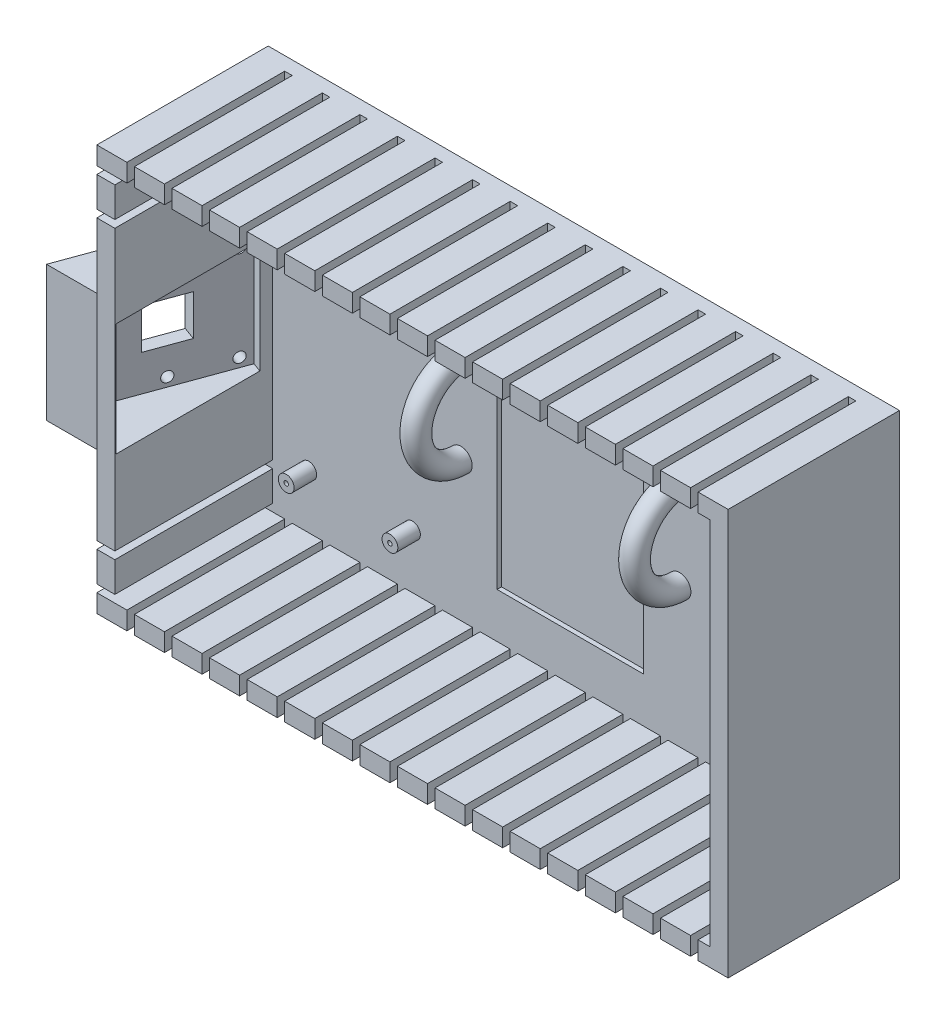
SolidWorks part; units mm, degrees
ref_plane "Front Plane" through (0, 0, 0) normal (1, 0, 0) x (0, 1, 0)
ref_plane "Top Plane" through (0, 0, 0) normal (0, 0, 1) x (0, 1, 0)
ref_plane "Right Plane" through (0, 0, 0) normal (0, 1, 0) x (-1, 0, 0)
sketch "Sketch1" plane through (0, 0, 0) normal (0, 0, 1) x (0, 1, 0)
  line L0 (-45, 0) -> (45, 0) construction
  line L1 (45, -70) -> (-45, -70)
  line L2 (45, -70) -> (45, 70)
  line L3 (45, 70) -> (-45, 70)
  line L4 (-45, -70) -> (-45, 70)
  line L5 (0, 70) -> (0, -70) construction
  point P9 (0, 0)
  dimension "D1" = 140
  dimension "D2" = 90
extrude "Boss-Extrude1" add sketch "Sketch1" along normal blind 3
sketch "Sketch2" plane through (0, 0, 3) normal (0, 0, 1) x (1, 0, 0)
  line L0 (-70, 45) -> (-70, -45) construction
  line L1 (-16.25, 31) -> (16.25, 31)
  line L2 (-16.25, 31) -> (-16.25, -31)
  line L3 (-16.25, -31) -> (16.25, -31)
  line L4 (16.25, 31) -> (16.25, -31)
  line L6 (-70, 0) -> (-16.25, 0) construction
  line L7 (16.25, 0) -> (70, 0) construction
  line L8 (70, -45) -> (70, 45) construction
  line L9 (0, 31) -> (0, 45) construction
  line L10 (70, 45) -> (-70, 45) construction
  line L11 (0, -31) -> (0, -45) construction
  line L12 (-70, -45) -> (70, -45) construction
  dimension "D1" = 62
  dimension "D2" = 32.5
extrude "Cut-Extrude1" cut sketch "Sketch2" against normal blind 1
sketch "Sketch6" plane through (0, 0, 3) normal (0, 0, 1) x (1, 0, 0)
  line L0 (-58, -45) -> (-58, -29) construction
  line L1 (-70, -45) -> (70, -45) construction
  line L2 (-58, 29) -> (-58, 45) construction
  line L3 (70, 45) -> (-70, 45) construction
  line L4 (-70, 45) -> (-70, -45) construction
  circle A0 centre (-58, 29) radius 1.75
  circle A1 centre (-35, 29) radius 1.75
  circle A2 centre (-35, -29) radius 1.75
  circle A3 centre (-58, -29) radius 1.75
  circle A4 centre (-58, 29) radius 0.5
  circle A5 centre (-35, 29) radius 0.5
  circle A6 centre (-58, -29) radius 0.5
  circle A7 centre (-35, -29) radius 0.5
  dimension "D1" = 3.5
  dimension "D2" = 23
  dimension "D3" = 58
  dimension "D4" = 12
  dimension "D5" = 1
extrude "Boss-Extrude2" add sketch "Sketch6" along normal blind 5 contours A1 | A0 | A3 | A2 region at (-59.7005, 29, 3) region at (-36.7005, 29, 3) region at (-36.7005, -29, 3) region at (-59.7005, -29, 3)
extrude "Boss-Extrude3" add sketch "Sketch6<3>" along normal blind 4 contours A4 | A5 | A6 | A7 region at (-58, 29, 3) region at (-35, 29, 3) region at (-58, -29, 3) region at (-35, -29, 3)
sketch "Sketch6<3>" plane through (0, 0, 3) normal (0, 0, 1) x (1, 0, 0) same geometry as "Sketch6"
sketch "Sketch7" plane through (0, 0, 3) normal (0, 0, 1) x (1, 0, 0)
  line L0 (-61.6667, 45) -> (-61.6667, 41)
  line L1 (-70, 45) -> (-63.3333, 45)
  line L2 (-70, 45) -> (-70, 41)
  line L3 (-70, 41) -> (-63.3333, 41)
  line L4 (-63.3333, 45) -> (-63.3333, 41)
  line L5 (-61.6667, 45) -> (-55, 45)
  line L6 (-55, 45) -> (-55, 41)
  line L7 (-61.6667, 41) -> (-55, 41)
  line L8 (-53.3333, 45) -> (-53.3333, 41)
  line L9 (-53.3333, 45) -> (-46.6667, 45)
  line L10 (-46.6667, 45) -> (-46.6667, 41)
  line L11 (-53.3333, 41) -> (-46.6667, 41)
  line L12 (-45, 45) -> (-45, 41)
  line L13 (-45, 45) -> (-38.3333, 45)
  line L14 (-38.3333, 45) -> (-38.3333, 41)
  line L15 (-45, 41) -> (-38.3333, 41)
  line L16 (-36.6667, 45) -> (-36.6667, 41)
  line L17 (-36.6667, 45) -> (-30, 45)
  line L18 (-30, 45) -> (-30, 41)
  line L19 (-36.6667, 41) -> (-30, 41)
  line L20 (-28.3333, 45) -> (-28.3333, 41)
  line L21 (-28.3333, 45) -> (-21.6667, 45)
  line L22 (-21.6667, 45) -> (-21.6667, 41)
  line L23 (-28.3333, 41) -> (-21.6667, 41)
  line L24 (-20, 45) -> (-20, 41)
  line L25 (-20, 45) -> (-13.3333, 45)
  line L26 (-13.3333, 45) -> (-13.3333, 41)
  line L27 (-20, 41) -> (-13.3333, 41)
  line L28 (-11.6667, 45) -> (-11.6667, 41)
  line L29 (-11.6667, 45) -> (-5, 45)
  line L30 (-5, 45) -> (-5, 41)
  line L31 (-11.6667, 41) -> (-5, 41)
  line L32 (-3.3333, 45) -> (-3.3333, 41)
  line L33 (-3.3333, 45) -> (3.3333, 45)
  line L34 (3.3333, 45) -> (3.3333, 41)
  line L35 (-3.3333, 41) -> (3.3333, 41)
  line L36 (5, 45) -> (5, 41)
  line L37 (5, 45) -> (11.6667, 45)
  line L38 (11.6667, 45) -> (11.6667, 41)
  line L39 (5, 41) -> (11.6667, 41)
  line L40 (13.3333, 45) -> (13.3333, 41)
  line L41 (13.3333, 45) -> (20, 45)
  line L42 (20, 45) -> (20, 41)
  line L43 (13.3333, 41) -> (20, 41)
  line L44 (21.6667, 45) -> (21.6667, 41)
  line L45 (21.6667, 45) -> (28.3333, 45)
  line L46 (28.3333, 45) -> (28.3333, 41)
  line L47 (21.6667, 41) -> (28.3333, 41)
  line L48 (30, 45) -> (30, 41)
  line L49 (30, 45) -> (36.6667, 45)
  line L50 (36.6667, 45) -> (36.6667, 41)
  line L51 (30, 41) -> (36.6667, 41)
  line L52 (38.3333, 45) -> (38.3333, 41)
  line L53 (38.3333, 45) -> (45, 45)
  line L54 (45, 45) -> (45, 41)
  line L55 (38.3333, 41) -> (45, 41)
  line L56 (46.6667, 45) -> (46.6667, 41)
  line L57 (46.6667, 45) -> (53.3333, 45)
  line L58 (53.3333, 45) -> (53.3333, 41)
  line L59 (46.6667, 41) -> (53.3333, 41)
  line L60 (55, 45) -> (55, 41)
  line L61 (55, 45) -> (61.6667, 45)
  line L62 (61.6667, 45) -> (61.6667, 41)
  line L63 (55, 41) -> (61.6667, 41)
  line L64 (63.3333, 45) -> (63.3333, 41)
  line L65 (63.3333, 45) -> (70, 45)
  line L66 (70, 45) -> (70, 41)
  line L67 (63.3333, 41) -> (70, 41)
  line L112 (0, 0) -> (0, 18.2112) construction
  line L113 (0, 0) -> (-20.7335, 0) construction
  line L114 (13.3333, -45) -> (20, -45)
  line L115 (20, -45) -> (20, -41)
  line L116 (13.3333, -41) -> (20, -41)
  line L117 (13.3333, -45) -> (13.3333, -41)
  line L118 (21.6667, -45) -> (28.3333, -45)
  line L119 (28.3333, -45) -> (28.3333, -41)
  line L120 (21.6667, -41) -> (28.3333, -41)
  line L121 (21.6667, -45) -> (21.6667, -41)
  line L122 (30, -45) -> (36.6667, -45)
  line L123 (36.6667, -45) -> (36.6667, -41)
  line L124 (30, -41) -> (36.6667, -41)
  line L125 (30, -45) -> (30, -41)
  line L126 (38.3333, -45) -> (45, -45)
  line L127 (45, -45) -> (45, -41)
  line L128 (38.3333, -41) -> (45, -41)
  line L129 (38.3333, -45) -> (38.3333, -41)
  line L130 (46.6667, -45) -> (53.3333, -45)
  line L131 (53.3333, -45) -> (53.3333, -41)
  line L132 (46.6667, -41) -> (53.3333, -41)
  line L133 (46.6667, -45) -> (46.6667, -41)
  line L134 (55, -45) -> (61.6667, -45)
  line L135 (61.6667, -45) -> (61.6667, -41)
  line L136 (55, -41) -> (61.6667, -41)
  line L137 (55, -45) -> (55, -41)
  line L138 (63.3333, -45) -> (70, -45)
  line L139 (70, -45) -> (70, -41)
  line L140 (63.3333, -41) -> (70, -41)
  line L141 (63.3333, -45) -> (63.3333, -41)
  line L142 (5, -45) -> (11.6667, -45)
  line L143 (11.6667, -45) -> (11.6667, -41)
  line L144 (5, -41) -> (11.6667, -41)
  line L145 (5, -45) -> (5, -41)
  line L146 (-3.3333, -45) -> (3.3333, -45)
  line L147 (3.3333, -45) -> (3.3333, -41)
  line L148 (-3.3333, -41) -> (3.3333, -41)
  line L149 (-3.3333, -45) -> (-3.3333, -41)
  line L150 (-11.6667, -45) -> (-5, -45)
  line L151 (-5, -45) -> (-5, -41)
  line L152 (-11.6667, -41) -> (-5, -41)
  line L153 (-11.6667, -45) -> (-11.6667, -41)
  line L154 (-20, -45) -> (-13.3333, -45)
  line L155 (-13.3333, -45) -> (-13.3333, -41)
  line L156 (-20, -41) -> (-13.3333, -41)
  line L157 (-20, -45) -> (-20, -41)
  line L158 (-28.3333, -45) -> (-21.6667, -45)
  line L159 (-21.6667, -45) -> (-21.6667, -41)
  line L160 (-28.3333, -41) -> (-21.6667, -41)
  line L161 (-28.3333, -45) -> (-28.3333, -41)
  line L162 (-36.6667, -45) -> (-30, -45)
  line L163 (-30, -45) -> (-30, -41)
  line L164 (-36.6667, -41) -> (-30, -41)
  line L165 (-36.6667, -45) -> (-36.6667, -41)
  line L166 (-70, -41) -> (-63.3333, -41)
  line L167 (-63.3333, -45) -> (-63.3333, -41)
  line L168 (-70, -45) -> (-63.3333, -45)
  line L169 (-70, -45) -> (-70, -41)
  line L170 (-61.6667, -45) -> (-55, -45)
  line L171 (-55, -45) -> (-55, -41)
  line L172 (-61.6667, -41) -> (-55, -41)
  line L173 (-61.6667, -45) -> (-61.6667, -41)
  line L174 (-53.3333, -45) -> (-46.6667, -45)
  line L175 (-46.6667, -45) -> (-46.6667, -41)
  line L176 (-53.3333, -41) -> (-46.6667, -41)
  line L177 (-53.3333, -45) -> (-53.3333, -41)
  line L178 (-45, -45) -> (-38.3333, -45)
  line L179 (-38.3333, -45) -> (-38.3333, -41)
  line L180 (-45, -41) -> (-38.3333, -41)
  line L181 (-45, -45) -> (-45, -41)
  line L226 (-70, 30.9933) -> (-60.5263, 30.9933) construction
  line L227 (-70, -30.9933) -> (-61.2912, -30.9933) construction
  line L228 (-70, 45) -> (-70, -45) construction
  line L229 (-70, 30.9933) -> (-66, 30.9933)
  line L230 (-70, 30.9933) -> (-70, -30.9933)
  line L231 (-70, -30.9933) -> (-66, -30.9933)
  line L232 (-66, 30.9933) -> (-66, -30.9933)
  line L233 (70, 45) -> (66, 45)
  line L234 (70, 45) -> (70, -45)
  line L235 (70, -45) -> (66, -45)
  line L236 (66, 45) -> (66, -45)
  line L237 (-70, 39.33) -> (-66, 39.33)
  line L238 (-70, 39.33) -> (-70, 32.6633)
  line L239 (-70, 32.6633) -> (-66, 32.6633)
  line L240 (-66, 39.33) -> (-66, 32.6633)
  line L246 (-70, -32.6633) -> (-66, -32.6633)
  line L247 (-70, -32.6633) -> (-70, -39.33)
  line L248 (-70, -39.33) -> (-66, -39.33)
  line L249 (-66, -32.6633) -> (-66, -39.33)
  line M13 (70, 45) -> (-70, 45)
  line M14 (-70, 45) -> (-70, -45)
  line M15 (-70, -45) -> (70, -45)
  line M16 (70, -45) -> (70, 45)
  dimension "D1" = 6.6667
  dimension "D2" = 4
  dimension "D5" = 1.67
  dimension "D6" = 1.67
  dimension "D4" = 4
  dimension "D7" = 1.67
  dimension "D8" = 1.67
  dimension "D3" = 17
sketch "Sketch9" plane through (0, 0, 3) normal (0, 0, 1) x (1, 0, 0)
  line L0 (-36.3093, 0) -> (22.5747, 0) construction
  line L1 (0, 0) -> (0, 22.2066) construction
  line L2 (-16.25, 31) -> (-16.25, -31) construction
  circle A0 centre (-24.25, -10) radius 2.5
  circle A1 centre (24.25, -10) radius 2.5
  dimension "D1" = 5
  dimension "D2" = 10
  dimension "D3" = 8
revolve "Revolve3" add sketch "Sketch9" angle 180 about L0 reverse direction yes
extrude "Boss-Extrude8" add sketch "Sketch7" along normal blind 35 contours L167 L166 M15 M14 | L173 L171 L172 M15 | L177 L175 L176 M15 | L181 L179 L180 M15 | L165 L163 L164 M15 | L161 L159 L160 M15 | L157 L155 L156 M15 | L153 L151 L152 M15 | L149 L147 L148 M15 | L145 L143 L144 M15 | L121 L119 L120 M15 | L125 L123 L124 M15 | L129 L127 L128 M15 | L133 L131 L132 M15 | L137 L135 L136 M15 | L140 L236 L138 M16 | L67 L236 L140 M16 | L60 L63 L62 M13 | L56 L59 L58 M13 | L48 L51 L50 M13 | L32 L35 L34 M13 | L28 L31 L30 M13 | L24 L27 L26 M13 | L20 L23 L22 M13 | L16 L19 L18 M13 | L0 L7 L6 M13 | L4 L3 M13 M14 | L240 L237 L239 M14 | L116 L115 L114 L117 | L138 L141 L140 L139 | L66 L67 L64 L65 | L53 L54 L55 L52 | L44 L47 L46 L45 | L42 L43 L40 L41 | L36 L39 L38 L37 | L28 L31 L30 L29 | L13 L14 L15 L12 | L9 L10 L11 L8 | L230 L231 L232 L229 | L247 L248 L249 L246 region at (-58.3333, 43, 3) region at (-66.6667, 43, 3) region at (-68, 35.9967, 3) region at (-33.3333, 43, 3) region at (-25, 43, 3) region at (-16.6667, 43, 3) region at (-66.6667, -43, 3) region at (-8.3333, 43, 3) region at (-58.3333, -43, 3) region at (0, 43, 3) region at (-50, -43, 3) region at (-41.6667, -43, 3) region at (-33.3333, -43, 3) region at (-25, -43, 3) region at (33.3333, 43, 3) region at (-16.6667, -43, 3) region at (-8.3333, -43, 3) region at (50, 43, 3) region at (0, -43, 3) region at (58.3333, 43, 3) region at (8.3333, -43, 3) region at (68, 0, 3) region at (68, -43, 3) region at (25, -43, 3) region at (33.3333, -43, 3) region at (58.3333, -43, 3) region at (41.6667, -43, 3) region at (50, -43, 3)
sketch "Sketch18" plane through (0, 0, 0) normal (0, 1, 0) x (-1, 0, 0)
  line L0 (70, 36.5) -> (82.6547, 36.5)
  line L1 (70, 38) -> (70, 0) construction
  line L2 (82.6547, 36.5) -> (70, 1.7314)
  line L3 (70, 1.7314) -> (70, 36.5)
  line L4 (63.3333, 38) -> (70, 38) construction
  dimension "D1" = 20
  dimension "D2" = 37
  dimension "D3" = 1.5
extrude "Boss-Extrude9" add sketch "Sketch18" along normal blind 15 and the other way blind 15
sketch "Sketch19" plane through (-61.2551, 0, -22.295) normal (-0.9397, 0, -0.342) x (0, -1, 0)
  line L0 (-10.5, 43.0684) -> (-10.5, 30.5684) construction
  line L1 (4.5, 38.5684) -> (-4.5, 38.5684)
  line L2 (4.5, 38.5684) -> (4.5, 47.5684)
  line L3 (4.5, 47.5684) -> (-4.5, 47.5684)
  line L4 (-4.5, 38.5684) -> (-4.5, 47.5684)
  line L5 (10.5, 43.0684) -> (10.5, 30.5684) construction
  line L6 (-10.5, 43.0684) -> (10.5, 43.0684) construction
  line L7 (-10.5, 30.5684) -> (10.5, 30.5684) construction
  line L8 (0, 43.0684) -> (0, 30.5684) construction
  line L9 (-15, 25.5684) -> (-15, 62.5684) construction
  line L10 (15, 25.5684) -> (15, 62.5684) construction
  line L14 (15, 25.5684) -> (-15, 25.5684) construction
  circle A0 centre (-10.5, 43.0684) radius 1.15
  circle A1 centre (10.5, 43.0684) radius 1.15
  circle A2 centre (10.5, 30.5684) radius 1.15
  circle A3 centre (-10.5, 30.5684) radius 1.15
  circle A4 centre (0, 43.0684) radius 1
  point P15 (0, 47.5684)
  point P16 (4.5, 43.0684)
  dimension "D1" = 2.3
  dimension "D3" = 21
  dimension "D4" = 12.5
  dimension "D6" = 2
  dimension "D2" = 9
  dimension "D5" = 5
extrude "Cut-Extrude2" cut sketch "Sketch19" against normal up to next contours A4 | L4 L1 L2 L3 A4 | A0 | A3 | A2 | A1 region at (-74.4898, 0, 14.067) region at (-75.9854, 10.5, 18.176) region at (-75.9854, -10.5, 18.176) region at (-71.7101, -10.5, 6.4298) region at (-71.7101, 10.5, 6.4298) region at (-75.9854, 0, 18.176)
sketch "Sketch21" plane through (-61.2551, 0, -22.295) normal (-0.9397, 0, -0.342) x (0, -1, 0)
  line L0 (0, 62.5684) -> (0, 25.5684) construction
  line L1 (-12.5, 58.0684) -> (12.5, 58.0684)
  line L2 (-12.5, 58.0684) -> (-12.5, 28.0684)
  line L3 (-12.5, 28.0684) -> (12.5, 28.0684)
  line L4 (12.5, 58.0684) -> (12.5, 28.0684)
  line L5 (15, 62.5684) -> (-15, 62.5684) construction
  line L6 (15, 25.5684) -> (-15, 25.5684) construction
  circle A0 centre (-10.5, 30.5684) radius 1.15 construction
  point P6 (-12.3404, 58.0684)
  dimension "D3" = 2.5
  dimension "D1" = 25
  dimension "D2" = 30
extrude "Cut-Extrude5" cut sketch "Sketch21" against normal up to next from offset 3 offset against normal yes
